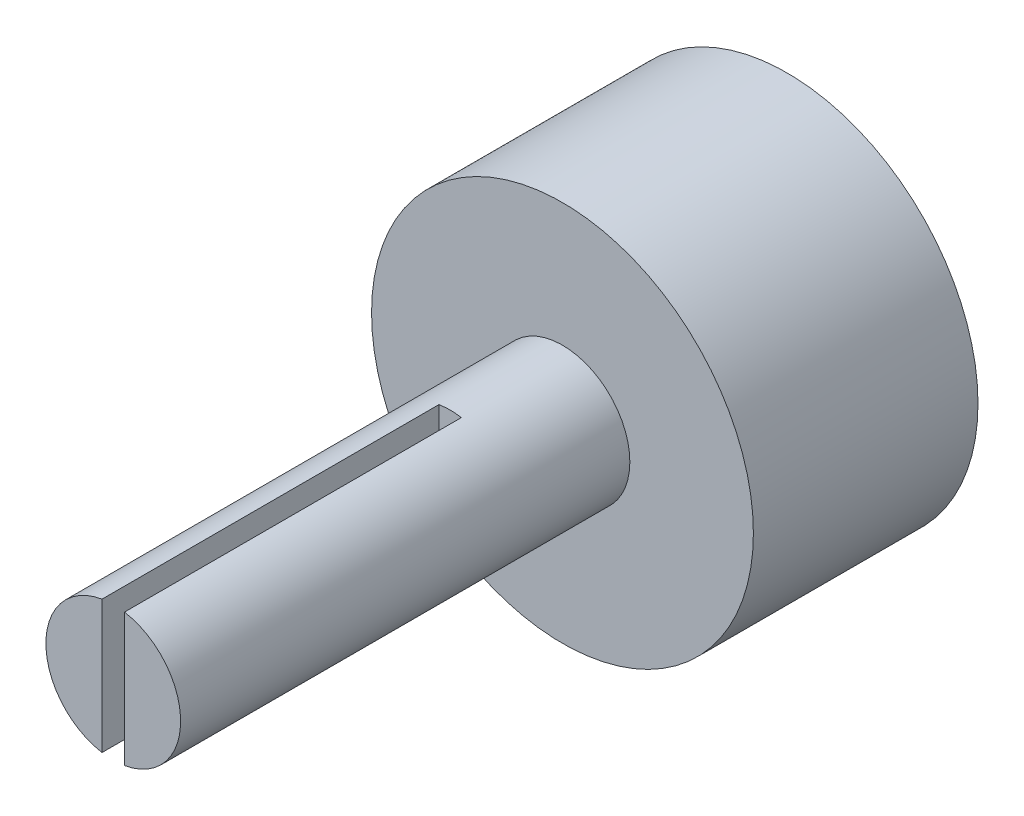
SolidWorks part; units mm, degrees
material "Cast Stainless Steel"
ref_plane "Front Plane" through (0, 0, 0) normal (0, 0, 1) x (1, 0, 0)
ref_plane "Top Plane" through (0, 0, 0) normal (0, 1, 0) x (1, 0, 0)
ref_plane "Right Plane" through (0, 0, 0) normal (1, 0, 0) x (0, 0, -1)
sketch "Sketch1" plane through (0, 0, 0) normal (0, 0, 1) x (1, 0, 0)
  circle A0 centre (0, 0) radius 8.5
  circle A1 centre (0, 0) radius 3
  dimension "D1" = 17
  dimension "D2" = 6
extrude "Boss-Extrude1" add sketch "Sketch1" along normal blind 20 contours A1 region at (0, 0, 0)
extrude "Boss-Extrude2" add sketch "Sketch1<3>" against normal blind 10 contours A1 | A0 A1 region at (-8.2596, 0, 0) region at (0, 0, 0)
sketch "Sketch1<3>" plane through (0, 0, 0) normal (0, 0, 1) x (1, 0, 0) same geometry as "Sketch1"
sketch "Sketch2" plane through (0, 0, 0) normal (1, 0, 0) x (0, 0, -1)
  line L1 (-5, 3) -> (-20, 3)
  line L2 (-5, 3) -> (-5, -3)
  line L3 (-5, -3) -> (-20, -3)
  line L4 (-20, 3) -> (-20, -3)
  line L5 (-5, 3) -> (-20, -3) construction
  line L6 (-5, -3) -> (-20, 3) construction
  point P0 (-12.5, 0)
  point P5 (0, 0)
  dimension "D1" = 6
  dimension "D2" = 15
  dimension "D3" = 5
extrude "Cut-Extrude1" cut sketch "Sketch2" against normal blind 0.5 and the other way blind 0.5
